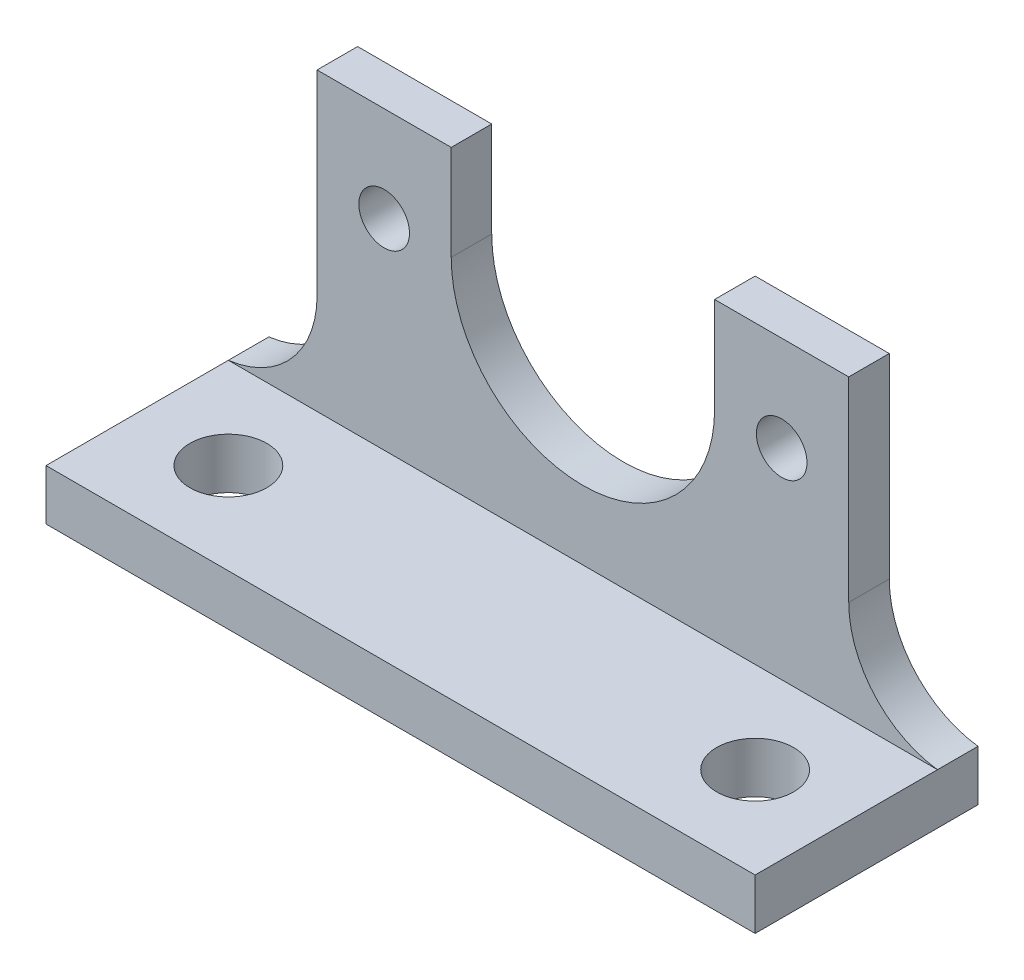
SolidWorks part; units mm, degrees
ref_plane "Front Plane" through (0, 0, 0) normal (0, 0, 1) x (1, 0, 0)
ref_plane "Top Plane" through (0, 0, 0) normal (0, 1, 0) x (1, 0, 0)
ref_plane "Right Plane" through (0, 0, 0) normal (1, 0, 0) x (0, 0, -1)
sketch "Sketch1" plane through (0, 0, 0) normal (0, 0, 1) x (1, 0, 0)
  line L0 (0, -5.2308) -> (0, 12.2462) construction
  line L1 (-21.4154, -5.2308) -> (23.5692, -5.2308) construction
  line L2 (-8.255, -5.2308) -> (-8.255, 0.7385)
  line L3 (-8.255, 0.7385) -> (-16.6624, 0.7385)
  line L4 (-12.4587, 0.7385) -> (-12.4587, -23.7538) construction
  line L5 (-16.6624, -5.2308) -> (-16.6624, -20.9788)
  line L6 (-16.6624, -5.2308) -> (-16.6624, 0.7385)
  line L7 (0, -5.2308) -> (0, -31.4165) construction
  line L8 (-16.6624, -20.9788) -> (16.6624, -20.9788)
  line L9 (16.6624, -5.2308) -> (16.6624, -20.9788)
  line L10 (16.6624, -5.2308) -> (16.6624, 0.7385)
  line L11 (8.255, 0.7385) -> (16.6624, 0.7385)
  line L12 (8.255, -5.2308) -> (8.255, 0.7385)
  circle A0 centre (0, -5.2308) radius 19.812 construction
  circle A1 centre (-12.4587, -5.2308) radius 1.5875
  circle A2 centre (0, -5.2308) radius 8.255 construction
  arc A3 (-8.255, -5.2308) -> (8.255, -5.2308) centre (0, -5.2308) ccw
  circle A4 centre (0, -5.2308) radius 12.4587 construction
  circle A5 centre (12.4587, -5.2308) radius 1.5875
  point P23 (0, -20.9788)
  dimension "D1" = 3.175
  dimension "D4" = 16.51
  dimension "D3" = 39.624
  dimension "D2" = 24.9174
  dimension "D5" = 15.748
extrude "Boss-Extrude1" add sketch "Sketch1" along normal blind 2.54
sketch "Sketch2" plane through (0, 0, 2.54) normal (0, 0, 1) x (1, 0, 0)
  line L1 (-22.225, -20.9788) -> (22.225, -20.9788)
  line L2 (-22.225, -20.9788) -> (-22.225, -17.8038)
  line L3 (-22.225, -17.8038) -> (22.225, -17.8038)
  line L4 (22.225, -20.9788) -> (22.225, -17.8038)
  line L5 (-16.6624, -20.9788) -> (16.6624, -20.9788) construction
  line L6 (0, 0) -> (0, -36.042) construction
  dimension "D1" = 3.175
  dimension "D2" = 44.45
  dimension "D3" = 22.225
extrude "Boss-Extrude2" add sketch "Sketch2" along normal blind 11.43 and the other way blind 2.54
sketch "Sketch3" plane through (0, -17.8038, 0) normal (0, 1, 0) x (1, 0, 0)
  line L0 (0, 5.0635) -> (0, -22.8454) construction
  line L1 (0, -8.255) -> (-22.7296, -8.255) construction
  line L2 (8.255, 0) -> (-8.255, 0) construction
  circle A0 centre (-16.51, -8.255) radius 2.413
  circle A2 centre (16.51, -8.255) radius 2.413
  dimension "D2" = 4.826
  dimension "D3" = 16.51
  dimension "D1" = 8.255
extrude "Cut-Extrude1" cut sketch "Sketch3" against normal through all
fillet "Fillet1" radius 6.35 2 edges at (-16.6624, -17.8038, 1.27) (16.6624, -17.8038, 1.27)
